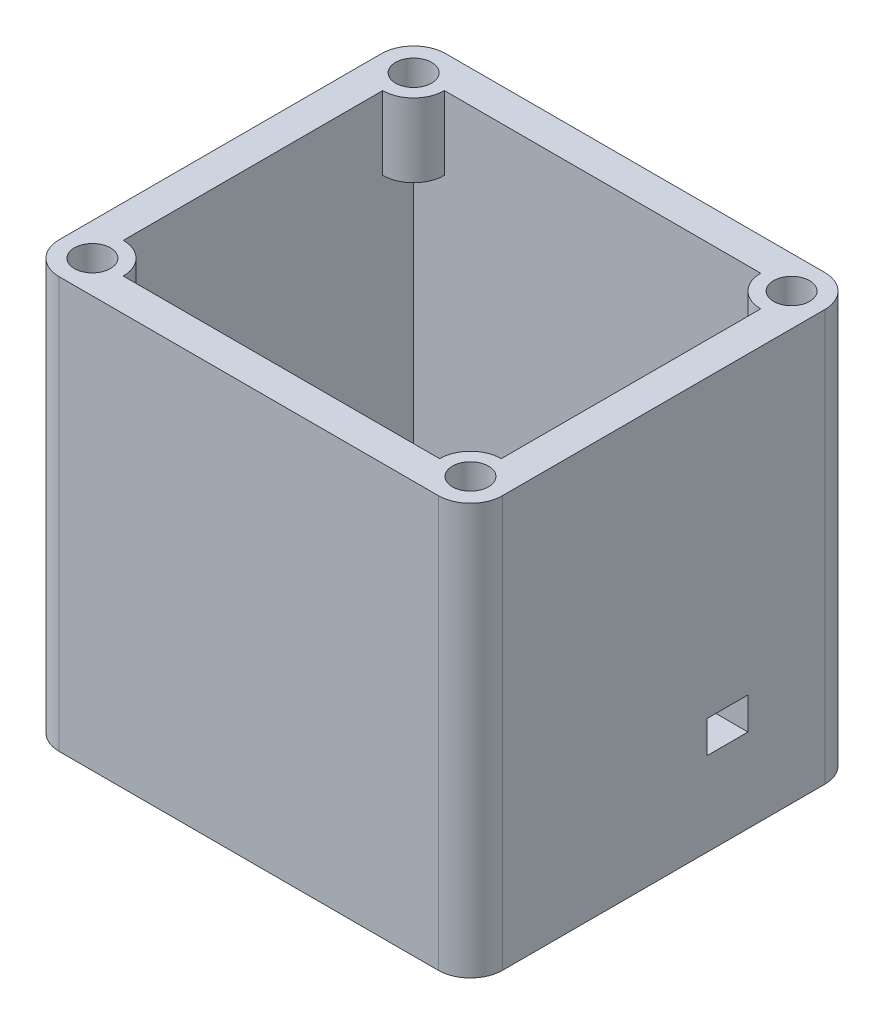
SolidWorks part; units mm, degrees
ref_plane "Front Plane" through (0, 0, 0) normal (0, 0, 1) x (1, 0, 0)
ref_plane "Top Plane" through (0, 0, 0) normal (0, 1, 0) x (1, 0, 0)
ref_plane "Right Plane" through (0, 0, 0) normal (1, 0, 0) x (0, 0, -1)
sketch "Sketch1" plane through (0, 0, 0) normal (0, 1, 0) x (1, 0, 0)
  line L1 (-34.505, -30.08) -> (34.505, -30.08)
  line L2 (-34.505, -30.08) -> (-34.505, 30.08)
  line L3 (-34.505, 30.08) -> (34.505, 30.08)
  line L4 (34.505, -30.08) -> (34.505, 30.08)
  line L5 (-34.505, -30.08) -> (34.505, 30.08) construction
  line L6 (-34.505, 30.08) -> (34.505, -30.08) construction
  point P0 (0, 0)
  dimension "Outer Box Length" = 69.01
  dimension "Outer Box Width" = 60.16
extrude "Boss-Extrude3" add sketch "Sketch1" along normal blind 64.008 contours L3 L4 L1 L2
sketch "Sketch2" plane through (0, 64.008, 0) normal (0, 1, 0) x (1, 0, 0)
  line L0 (-34.505, 30.08) -> (34.505, 30.08) construction
  line L1 (29.425, -25) -> (-29.425, -25)
  line L2 (29.425, -25) -> (29.425, 25)
  line L3 (29.425, 25) -> (-29.425, 25)
  line L4 (-29.425, -25) -> (-29.425, 25)
  line L5 (29.425, -25) -> (-29.425, 25) construction
  line L6 (29.425, 25) -> (-29.425, -25) construction
  line L7 (-34.505, -30.08) -> (-34.505, 30.08) construction
  point P0 (0, 0)
  dimension "D1" = 5.08
  dimension "D2" = 5.08
extrude "Cut-Extrude4" cut sketch "Sketch2" against normal blind 58.928 contours L4 L3 L2 L1
fillet "Fillet1" radius 5 4 edges at (34.505, 32.004, -30.08) (-34.505, 32.004, -30.08) (-34.505, 32.004, 30.08) (34.505, 32.004, 30.08)
sketch "Sketch3" plane through (0, 64.008, 0) normal (0, 1, 0) x (1, 0, 0)
  circle A0 centre (-29.425, 25) radius 4.8067
  circle A2 centre (29.425, 25) radius 4.8067
  circle A3 centre (-29.425, -25) radius 4.8067
  circle A4 centre (29.425, -25) radius 4.8067
  circle A5 centre (-29.425, 25) radius 2.8067
  circle A6 centre (29.425, 25) radius 2.8067
  circle A7 centre (29.425, -25) radius 2.8067
  circle A8 centre (-29.425, -25) radius 2.8067
  dimension "D1" = 9.6134
extrude "Boss-Extrude4" add sketch "Sketch3" against normal blind 11.43 contours A2 | A0 | A3 | A4
extrude "Cut-Extrude5" cut sketch "Sketch3<3>" against normal blind 6.35 contours A5 | A8 | A7 | A6
sketch "Sketch3<3>" plane through (0, 64.008, 0) normal (0, 1, 0) x (1, 0, 0) same geometry as "Sketch3"
sketch "Sketch9" plane through (0, 5.08, 0) normal (0, 1, 0) x (1, 0, 0)
  line L0 (-29.425, -20.1933) -> (-29.425, 20.1933) construction
  line L1 (29.425, 25) -> (-29.425, 25) construction
  line L2 (29.425, -25) -> (29.425, 25) construction
  line L3 (29.425, -25) -> (-29.425, -25) construction
  line L4 (-29.425, -25) -> (-29.425, 25) construction
  circle A0 centre (-23.475, 19.1) radius 4.8067
  circle A1 centre (23.275, 19.1) radius 4.8067
  circle A2 centre (23.275, -18.9) radius 4.8067
  circle A3 centre (-23.475, -19.15) radius 4.8067
  circle A4 centre (-23.475, -19.15) radius 2.8067
  circle A5 centre (23.275, -18.9) radius 2.8067
  circle A6 centre (23.275, 19.1) radius 2.8067
  circle A7 centre (-23.475, 19.1) radius 2.8067
  dimension "D3" = 9.6134
  dimension "D1" = 5.95
  dimension "D2" = 5.9
  dimension "D4" = 5.9
  dimension "D5" = 6.15
  dimension "D6" = 6.15
  dimension "D7" = 6.1
  dimension "D8" = 5.95
  dimension "D9" = 5.85
  dimension "D10" = 2
extrude "Boss-Extrude5" add sketch "Sketch9" along normal blind 6.35
sketch "Sketch10" plane through (0, 5.08, 0) normal (0, 1, 0) x (1, 0, 0)
  line L1 (-14.2125, -12) -> (14.2125, -12)
  line L2 (-14.2125, -12) -> (-14.2125, 12)
  line L3 (-14.2125, 12) -> (14.2125, 12)
  line L4 (14.2125, -12) -> (14.2125, 12)
  line L5 (-14.2125, -12) -> (14.2125, 12) construction
  line L6 (-14.2125, 12) -> (14.2125, -12) construction
  circle A0 centre (14.2125, 12) radius 2.159
  circle A1 centre (14.2125, -12) radius 2.159
  circle A2 centre (-14.2125, 12) radius 2.159
  circle A3 centre (-14.2125, -12) radius 2.159
  point P0 (0, 0)
  dimension "D3" = 4.318
  dimension "D1" = 28.425
  dimension "D2" = 24
extrude "Cut-Extrude6" cut sketch "Sketch10" against normal up to surface (5.08 mm away) contours A0 | A1 | A3 | A2 up to face at (0, 0, 0)
sketch "Sketch12" plane through (0, 5.08, 0) normal (0, 1, 0) x (1, 0, 0)
  line L0 (-29.425, -25) -> (-29.425, 25) construction
  circle A0 centre (-23.475, 19.1) radius 4.8067 construction
  text T0 "1"
  dimension "D1" = 2
  dimension "D2" = 10
extrude "Boss-Extrude6" add sketch "Sketch12" along normal blind 1
sketch "Face 1 Connector Holes" plane through (-34.505, 0, 0) normal (-1, 0, 0) x (0, 0, 1)
  line L0 (-25.08, 64.008) -> (-25.08, 0) construction
  line L1 (-25.08, 63.83) -> (25.08, 63.83)
  line L2 (-25.08, 63.83) -> (-25.08, 13.03)
  line L3 (-25.08, 13.03) -> (25.08, 13.03)
  line L4 (25.08, 63.83) -> (25.08, 13.03)
  line L5 (25.08, 0) -> (25.08, 64.008) construction
  line L6 (25.08, 0) -> (-25.08, 0) construction
  dimension "D1" = 50.8
  dimension "D2" = 13.03
sketch "Face 2 Connector Holes" plane through (0, 0, -30.08) normal (0, 0, -1) x (-1, 0, 0)
  line L0 (29.505, 0) -> (29.505, 64.008) construction
  line L1 (29.505, 13.03) -> (-29.505, 13.03)
  line L2 (29.505, 13.03) -> (29.505, 63.83)
  line L3 (29.505, 63.83) -> (-29.505, 63.83)
  line L4 (-29.505, 13.03) -> (-29.505, 63.83)
  line L5 (-29.505, 64.008) -> (-29.505, 0) construction
  line L6 (29.505, 0) -> (-29.505, 0) construction
  line L8 (18.505, 13.03) -> (12.105, 13.03)
  line L9 (18.505, 13.03) -> (18.505, 18.03)
  line L10 (18.505, 18.03) -> (12.105, 18.03)
  line L11 (12.105, 13.03) -> (12.105, 18.03)
  line L12 (-7.845, 13.03) -> (-18.245, 13.03)
  line L13 (-7.845, 13.03) -> (-7.845, 18.03)
  line L14 (-7.845, 18.03) -> (-18.245, 18.03)
  line L15 (-18.245, 13.03) -> (-18.245, 18.03)
  dimension "D1" = 13.03
  dimension "D2" = 50.8
  dimension "D3" = 11
  dimension "D4" = 6.4
  dimension "D5" = 5
  dimension "D6" = 37.35
  dimension "D7" = 10.4
  dimension "D8" = 5
extrude "Cut-Extrude7" cut sketch "Face 2 Connector Holes" against normal up to surface (5.08 mm away) contours L14 L15 L12 L13 | L10 L11 L8 L9 up to face at (0, 43.561, -25)
sketch "Face 3 Connector Holes" plane through (34.505, 0, 0) normal (1, 0, 0) x (0, 0, -1)
  line L0 (-25.08, 64.008) -> (-25.08, 0) construction
  line L1 (-25.08, 63.83) -> (25.08, 63.83)
  line L2 (-25.08, 63.83) -> (-25.08, 13.03)
  line L3 (-25.08, 13.03) -> (25.08, 13.03)
  line L4 (25.08, 63.83) -> (25.08, 13.03)
  line L5 (25.08, 0) -> (25.08, 64.008) construction
  line L6 (-25.08, 0) -> (25.08, 0) construction
  line L8 (6.73, 13.03) -> (13.13, 13.03)
  line L9 (6.73, 13.03) -> (6.73, 18.03)
  line L10 (6.73, 18.03) -> (13.13, 18.03)
  line L11 (13.13, 13.03) -> (13.13, 18.03)
  dimension "D4" = 6.4
  dimension "D5" = 5
  dimension "D1" = 50.8
  dimension "D2" = 13.03
  dimension "D3" = 11.95
sketch "Face 4 Connector Holes" plane through (0, 0, 30.08) normal (0, 0, 1) x (1, 0, 0)
  line L0 (-29.505, 64.008) -> (-29.505, 0) construction
  line L1 (-29.505, 63.83) -> (29.505, 63.83)
  line L2 (-29.505, 63.83) -> (-29.505, 13.03)
  line L3 (-29.505, 13.03) -> (29.505, 13.03)
  line L4 (29.505, 63.83) -> (29.505, 13.03)
  line L5 (29.505, 0) -> (29.505, 64.008) construction
  line L6 (-29.505, 0) -> (29.505, 0) construction
  dimension "D1" = 50.8
  dimension "D2" = 13.03
extrude "Cut-Extrude8" cut sketch "Face 3 Connector Holes" against normal up to surface (5.08 mm away) contours L10 L11 L8 L9 up to face at (29.425, 43.561, 0)
equation "\"PCB Length\"= 56.85mm"
equation "\"PCB Width\"= 48mm"
equation "\"PCB Height\"= 2in"
equation "\"Insert Height\"= 0.25in"
equation "\"Wall Thickness\"= 0.2in"
equation "\"Support Hole OD\"= 0.17in"
equation "\"PCB Margin\"= 1mm"
equation "\"Screw Length\"= 7in / 16"
equation "\"Insert OD Size\"= 0.221in"
equation "\"PCB d1\"= 4.95mm"
equation "\"PCB d2\"= 4.9mm"
equation "\"PCB d3\"= 4.9mm"
equation "\"PCB d4\"= 5.15mm"
equation "\"PCB d5\"= 5.15mm"
equation "\"PCB d6\"= 5.1mm"
equation "\"PCB d7\"= 4.85mm"
equation "\"PCB d8\"= 4.95mm"
equation "\"Insert Wall Thickness\"= 2mm"
equation "\"PCB Underside Washer\"= 0.07in"
equation "\"Outer Box Length@Sketch1\" = 2 * \"Wall Thickness\" + 2 * \"PCB Margin\" + \"PCB Length\""
equation "\"Outer Box Width@Sketch1\"=2 * \"Wall Thickness\" + 2 * \"PCB Margin\" + \"PCB Width\""
equation "\"D1@Boss-Extrude3\"=\"Wall Thickness\"+\"Insert Height\"+\"PCB Underside Washer\"+\"PCB Height\""
equation "\"D2@Sketch2\"=\"Wall Thickness\""
equation "\"D1@Sketch2\"=\"Wall Thickness\" "
equation "\"D1@Cut-Extrude4\"=\"PCB Height\"+\"PCB Underside Washer\"+\"Insert Height\""
equation "\"D1@Sketch3\"=\"Insert OD Size\"+ 2 * \"Insert Wall Thickness\""
equation "\"D1@Boss-Extrude4\"=\"Insert Height\"+ \"Wall Thickness\""
equation "\"D1@Cut-Extrude5\"=\"Insert Height\""
equation "\"D1@Sketch9\"=\"PCB d1\" + \"PCB Margin\""
equation "\"D4@Sketch9\"=\"PCB d3\"+\"PCB Margin\""
equation "\"D5@Sketch9\"=\"PCB d4\"+\"PCB Margin\""
equation "\"D6@Sketch9\"=\"PCB d5\" + \"PCB Margin\""
equation "\"D2@Sketch9\"=\"PCB d2\" + \"PCB Margin\" "
equation "\"D7@Sketch9\"=\"PCB d6\"+\"PCB Margin\""
equation "\"D8@Sketch9\"= \"PCB d8\"+\"PCB Margin\""
equation "\"D9@Sketch9\"=\"PCB d7\"+\"PCB Margin\""
equation "\"D10@Sketch9\"=\"Insert Wall Thickness\""
equation "\"D1@Boss-Extrude5\"=\"Insert Height\""
equation "\"D1@Sketch10\"=\"PCB Length\"/2"
equation "\"D2@Sketch10\"=\"PCB Width\"/2"
equation "\"D3@Sketch10\"=\"Support Hole OD\""
equation "\"D3@Sketch9\"=\"Insert OD Size\" + 2 * \"Insert Wall Thickness\""
equation "\"D1@Face 2 Connector Holes\"=\"Wall Thickness\" + \"Insert Height\"+1.6mm"
equation "\"D2@Face 2 Connector Holes\" = \"PCB Height\""
equation "\"D1@Face 1 Connector Holes\" = \"PCB Height\""
equation "\"D2@Face 1 Connector Holes\"=\"Wall Thickness\" +\"Insert Height\"+ 1.6mm"
equation "\"D1@Face 3 Connector Holes\" = \"PCB Height\""
equation "\"D2@Face 3 Connector Holes\"=\"Wall Thickness\" +\"Insert Height\"+ 1.6mm"
equation "\"D1@Face 4 Connector Holes\" = \"PCB Height\""
equation "\"D2@Face 4 Connector Holes\"=\"Wall Thickness\" +\"Insert Height\"+ 1.6mm"
equation "\"D6@Face 2 Connector Holes\"=36.35mm + \"PCB Margin\""
equation "\"D3@Face 2 Connector Holes\"=10mm + \"PCB Margin\""
equation "\"D3@Face 3 Connector Holes\"=10.95mm + \"PCB Margin\""
